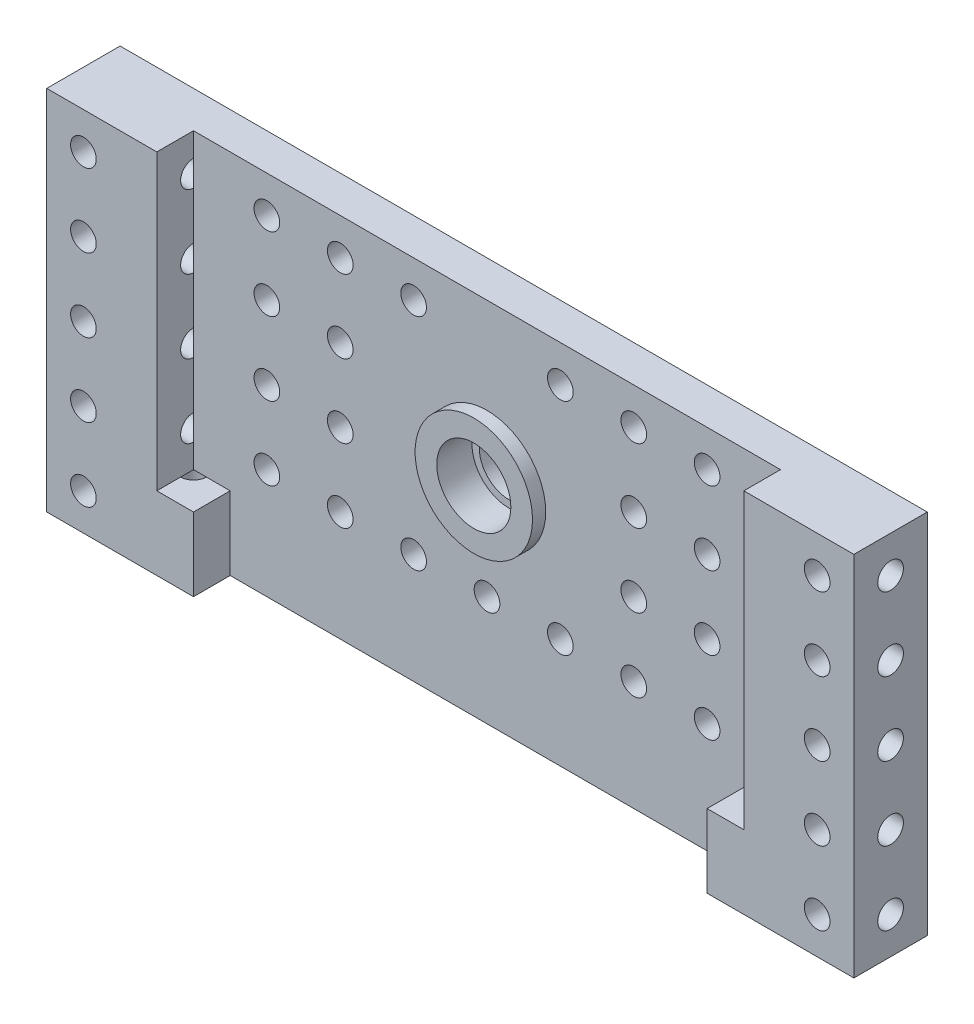
SolidWorks part; units mm, degrees
note: The reader was unsure of these and kept them because the rebuilt part matched: shared geometry of "Esquisse2<2>", "Esquisse5<2>".
ref_plane "Plan de face" through (0, 0, 0) normal (0, 0, 1) x (1, 0, 0)
ref_plane "Plan de dessus" through (0, 0, 0) normal (0, 1, 0) x (1, 0, 0)
ref_plane "Plan de droite" through (0, 0, 0) normal (1, 0, 0) x (0, 0, -1)
sketch "Esquisse1" plane through (0, 0, 0) normal (0, 0, 1) x (1, 0, 0)
  line L0 (45, 40) -> (45, 0) construction
  line L1 (0, 0) -> (90, 0)
  line L2 (0, 0) -> (0, 40)
  line L3 (0, 40) -> (90, 40)
  line L4 (90, 0) -> (90, 40)
  line L5 (0, 35) -> (90, 35) construction
  line L6 (5, 40) -> (5, 0) construction
  circle A0 centre (45, 19) radius 5.05
  circle A1 centre (5, 35) radius 1.75 construction
  circle A2 centre (15, 35) radius 1.75
  circle A3 centre (25, 35) radius 1.75
  circle A4 centre (35, 35) radius 1.75
  circle A5 centre (45, 35) radius 1.75 construction
  circle A6 centre (55, 35) radius 1.75
  circle A7 centre (65, 35) radius 1.75
  circle A8 centre (75, 35) radius 1.75
  circle A9 centre (85, 35) radius 1.75 construction
  circle A10 centre (15, 25) radius 1.75
  circle A11 centre (25, 25) radius 1.75
  circle A12 centre (35, 25) radius 1.75 construction
  circle A13 centre (45, 25) radius 1.75 construction
  circle A14 centre (55, 25) radius 1.75 construction
  circle A15 centre (65, 25) radius 1.75
  circle A16 centre (75, 25) radius 1.75
  circle A17 centre (85, 25) radius 1.75 construction
  circle A18 centre (15, 15) radius 1.75
  circle A19 centre (25, 15) radius 1.75
  circle A20 centre (35, 15) radius 1.75 construction
  circle A21 centre (45, 15) radius 1.75 construction
  circle A22 centre (55, 15) radius 1.75 construction
  circle A23 centre (65, 15) radius 1.75
  circle A24 centre (75, 15) radius 1.75
  circle A25 centre (85, 15) radius 1.75 construction
  circle A26 centre (5, 25) radius 1.75 construction
  circle A27 centre (5, 15) radius 1.75 construction
  circle A28 centre (5, 5) radius 1.75 construction
  circle A29 centre (15, 5) radius 1.75
  circle A30 centre (25, 5) radius 1.75
  circle A31 centre (35, 5) radius 1.75
  circle A32 centre (45, 5) radius 1.75
  circle A33 centre (55, 5) radius 1.75
  circle A34 centre (65, 5) radius 1.75
  circle A35 centre (75, 5) radius 1.75
  circle A36 centre (85, 5) radius 1.75 construction
  dimension "D3" = 10.1
  dimension "D7" = 3.5
  dimension "D1" = 90
  dimension "D2" = 40
  dimension "D4" = 19
  dimension "D5" = 40
  dimension "D6" = 5
  dimension "D8" = 9
  dimension "D9" = 4
extrude "Boss.-Extru.1" add sketch "Esquisse1" along normal blind 10
sketch "Esquisse2" plane through (90, 0, 0) normal (1, 0, 0) x (0, 0, -1)
  line L0 (-5, 30) -> (-5, 0) construction
  line L1 (-10, 40) -> (0, 40) construction
  line L4 (-10, 0) -> (-10, 40) construction
  circle A0 centre (-5, 35) radius 1.75
  circle A1 centre (-5, 25) radius 1.75
  circle A2 centre (-5, 15) radius 1.75
  circle A3 centre (-5, 5) radius 1.75
  circle A4 centre (-5, -5) radius 1.75
  dimension "D1" = 3.5
  dimension "D2" = 5
  dimension "D4" = 5
  dimension "D3" = 5
sketch "Esquisse3" plane through (0, 0, 10) normal (0, 0, 1) x (1, 0, 0)
  line L0 (90, 40) -> (0, 40) construction
  line L1 (5, 40) -> (85, 40)
  line L2 (5, 40) -> (5, 0)
  line L3 (5, 0) -> (85, 0)
  line L4 (85, 40) -> (85, 0)
  line L5 (0, 0) -> (90, 0) construction
  line L6 (0, 40) -> (0, 0) construction
  line L7 (90, 0) -> (90, 40) construction
  dimension "D1" = 5
  dimension "D2" = 5
extrude "Enlèv. mat.-Extru.3" cut sketch "Esquisse3" against normal blind 5
sketch "Esquisse4" plane through (0, 0, 0) normal (0, -1, 0) x (1, 0, 0)
  line L0 (0, 0) -> (0, 10)
  line L1 (0, 10) -> (10, 10)
  line L2 (0, 10) -> (5, 10) construction
  line L3 (10, 10) -> (10, 5)
  line L4 (10, 5) -> (80, 5)
  line L5 (80, 5) -> (80, 10)
  line L6 (80, 10) -> (90, 10)
  line L7 (90, 10) -> (90, 0)
  line L8 (90, 0) -> (0, 0)
  line L9 (5, 19.8513) -> (5, -6.1337) construction
  line L10 (85, 22.1783) -> (85, -6.1337) construction
  line L11 (95.1718, 5) -> (-12.8404, 5) construction
  line L12 (5, 5) -> (85, 5) construction
  circle A0 centre (5, 5) radius 1.75
  circle A1 centre (85, 5) radius 1.75
  point P33 (10, 7.5)
  dimension "D1" = 3.5
  dimension "D2" = 5
  dimension "D3" = 5
  dimension "D4" = 5
  dimension "D5" = 10
  dimension "D6" = 10
extrude "Boss.-Extru.2" add sketch "Esquisse4" along normal blind 10
extrude "Enlèv. mat.-Extru.1" cut sketch "Esquisse2" against normal up to vertex (5 mm away)
extrude "Enlèv. mat.-Extru.2" cut sketch "Esquisse2<2>" along normal up to surface (5 mm away) from surface at -90 up to face at (5, 16, 7.35) starting at face at (0, 15, 5)
sketch "Esquisse2<2>" plane through (90, 0, 0) normal (1, 0, 0) x (0, 0, -1) same geometry as "Esquisse2"
sketch "Esquisse5" plane through (90, 0, 0) normal (1, 0, 0) x (0, 0, -1)
  line L0 (-10, -10) -> (-10, 40) construction
  line L1 (-10, 40) -> (0, 40)
  line L2 (-10, 40) -> (-10, -10)
  line L3 (-10, -10) -> (0, -10)
  line L4 (0, 40) -> (0, -10)
  line L5 (0, -10) -> (0, 40) construction
  line L6 (0, -10) -> (-10, -10) construction
  circle A0 centre (-5, 35) radius 1.75
  circle A1 centre (-5, 25) radius 1.75
  circle A2 centre (-5, 15) radius 1.75
  circle A3 centre (-5, 5) radius 1.75
  circle A4 centre (-5, -5) radius 1.75
  circle A5 centre (-5, 35) radius 1.75 construction
  circle A6 centre (-5, 25) radius 1.75 construction
  circle A7 centre (-5, 15) radius 1.75 construction
  circle A8 centre (-5, 5) radius 1.75 construction
  circle A9 centre (-5, -5) radius 1.75 construction
extrude "Boss.-Extru.3" add sketch "Esquisse5" along normal blind 10
extrude "Boss.-Extru.4" add sketch "Esquisse5<2>" against normal blind 10 from vertex
sketch "Esquisse5<2>" plane through (90, 0, 0) normal (1, 0, 0) x (0, 0, -1) same geometry as "Esquisse5"
sketch "Esquisse6" plane through (0, 0, 0) normal (0, 0, -1) x (-1, 0, 0)
  line L0 (-15, 35) -> (-75, 35) construction
  circle A0 centre (-95, 35) radius 1.75
  circle A1 centre (5, 35) radius 1.75
  circle A2 centre (5, 25) radius 1.75
  circle A3 centre (5, 15) radius 1.75
  circle A4 centre (5, 5) radius 1.75
  circle A5 centre (5, -5) radius 1.75
  circle A6 centre (-95, 25) radius 1.75
  circle A7 centre (-95, 15) radius 1.75
  circle A8 centre (-95, 5) radius 1.75
  circle A9 centre (-95, -5) radius 1.75
  dimension "D2" = 3.5
  dimension "D1" = 20
  dimension "D3" = 2
  dimension "D4" = 5
extrude "Enlèv. mat.-Extru.4" cut sketch "Esquisse6" against normal blind 10
sketch "Esquisse7" plane through (0, 0, 0) normal (0, 0, -1) x (-1, 0, 0)
  circle A0 centre (-45, 19) radius 5.05
  circle A1 centre (-45, 19) radius 4.05
  circle A2 centre (-45, 19) radius 5.05 construction
  dimension "D1" = 1
extrude "Boss.-Extru.5" add sketch "Esquisse7" against normal offset from surface (2 mm away) 3 up to face at (50.05, 19, 5)
sketch "Esquisse8" plane through (0, 0, 5) normal (0, 0, 1) x (1, 0, 0)
  circle A0 centre (45, 19) radius 8
  circle A1 centre (45, 19) radius 5.05
  circle A2 centre (45, 19) radius 5.05 construction
  dimension "D1" = 16
extrude "Boss.-Extru.6" add sketch "Esquisse8" along normal blind 1.8
